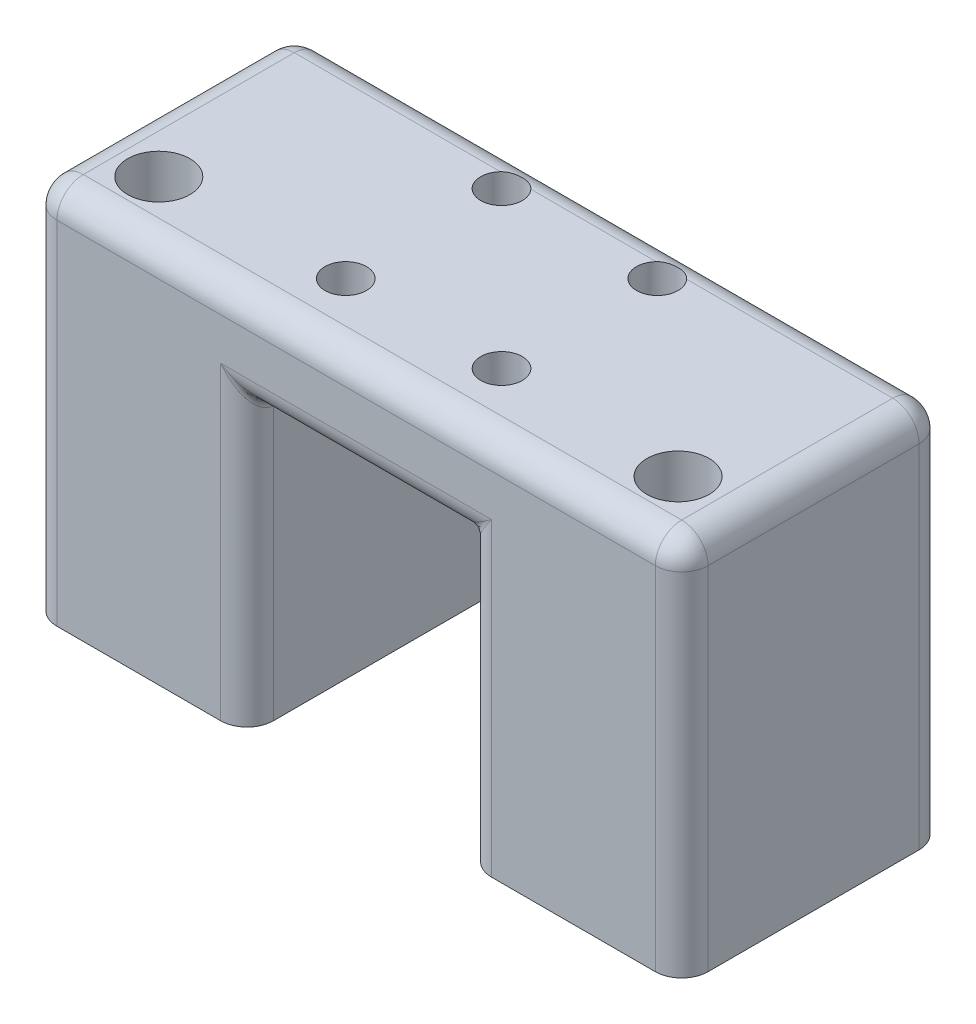
SolidWorks part; units mm, degrees
material "PLA"
ref_plane "Front Plane" through (0, 0, 0) normal (0, 0, 1) x (1, 0, 0)
ref_plane "Top Plane" through (0, 0, 0) normal (0, 1, 0) x (1, 0, 0)
ref_plane "Right Plane" through (0, 0, 0) normal (1, 0, 0) x (0, 0, -1)
sketch "Sketch1" plane through (0, 0, 0) normal (0, 1, 0) x (1, 0, 0)
  line L0 (-7.5, 8.8) -> (7.5, 8.8) construction
  line L1 (-31.35, -12.7) -> (31.35, -12.7)
  line L2 (-31.35, -12.7) -> (-31.35, 12.7)
  line L3 (-31.35, 12.7) -> (31.35, 12.7)
  line L4 (31.35, -12.7) -> (31.35, 12.7)
  line L5 (-31.35, -12.7) -> (31.35, 12.7) construction
  line L6 (-31.35, 12.7) -> (31.35, -12.7) construction
  line L7 (7.5, 8.8) -> (7.5, -6.2) construction
  line L8 (7.5, -6.2) -> (-7.5, -6.2) construction
  line L9 (-7.5, -6.2) -> (-7.5, 8.8) construction
  line L10 (-25, -6.7) -> (25, -6.7) construction
  circle A0 centre (-7.5, -6.2) radius 1.125
  circle A1 centre (-7.5, 8.8) radius 1.125
  circle A2 centre (7.5, 8.8) radius 1.125
  circle A3 centre (7.5, -6.2) radius 1.125
  circle A4 centre (-25, -6.7) radius 1.75
  circle A5 centre (25, -6.7) radius 1.75
  point P0 (0, 0)
  point P15 (0, -6.2)
  point P19 (0, -6.7)
  dimension "D6" = 2.25
  dimension "D8" = 3.5
  dimension "D1" = 62.7
  dimension "D2" = 25.4
  dimension "D3" = 15
  dimension "D4" = 15
  dimension "D5" = 6
  dimension "D7" = 50
  dimension "D9" = 0.5
extrude "Boss-Extrude1" add sketch "Sketch1" along normal mid plane 1.5
sketch "Sketch2" plane through (0, -0.75, 0) normal (0, -1, 0) x (1, 0, 0)
  line L0 (31.35, -12.7) -> (-31.35, -12.7) construction
  line L1 (-31.35, 12.7) -> (-10.5, 12.7)
  line L2 (-31.35, 12.7) -> (-31.35, -12.7)
  line L3 (-31.35, -12.7) -> (-10.5, -12.7)
  line L4 (-10.5, 12.7) -> (-10.5, -12.7)
  line L6 (31.35, 12.7) -> (10.5, 12.7)
  line L7 (31.35, 12.7) -> (31.35, -12.7)
  line L8 (31.35, -12.7) -> (10.5, -12.7)
  line L9 (10.5, 12.7) -> (10.5, -12.7)
  circle A0 centre (-25, 6.7) radius 1.75
  circle A1 centre (25, 6.7) radius 1.75
  circle A2 centre (25, 6.7) radius 1.75 construction
  circle A3 centre (-25, 6.7) radius 1.75 construction
  dimension "D1" = 21
extrude "Boss-Extrude2" add sketch "Sketch2" along normal blind 27.278
sketch "Sketch3" plane through (0, 0.75, 0) normal (0, 1, 0) x (1, 0, 0)
  circle A0 centre (-25, -6.7) radius 3
  circle A1 centre (25, -6.7) radius 3
  dimension "D1" = 6
extrude "Cut-Extrude1" cut sketch "Sketch3" against normal blind 19.05
sketch "Sketch4" plane through (0, 0.75, 0) normal (0, 1, 0) x (1, 0, 0)
  line L1 (-31.35, -12.7) -> (31.35, -12.7)
  line L2 (-31.35, -12.7) -> (-31.35, 12.7)
  line L3 (-31.35, 12.7) -> (31.35, 12.7)
  line L4 (31.35, -12.7) -> (31.35, 12.7)
  line L5 (-31.35, -12.7) -> (31.35, 12.7) construction
  line L6 (-31.35, 12.7) -> (31.35, -12.7) construction
  circle A0 centre (-25, -6.7) radius 3
  circle A1 centre (25, -6.7) radius 3
  circle A2 centre (-7.5, 8.8) radius 2
  circle A3 centre (7.5, 8.8) radius 2
  circle A4 centre (-7.5, -6.2) radius 2
  circle A5 centre (7.5, -6.2) radius 2
  circle A6 centre (-25, -6.7) radius 3 construction
  circle A7 centre (25, -6.7) radius 3 construction
  point P22 (0, 0)
  dimension "D1" = 4
extrude "Boss-Extrude3" add sketch "Sketch4" along normal blind 7.62
fillet "Fillet1" radius 2.54 14 edges at (0, -0.75, -12.7) (31.35, 8.37, 0) (0, 8.37, -12.7) (-31.35, 8.37, 0) (0, 8.37, 12.7) (0, -0.75, 12.7) (31.35, -9.829, 12.7) (31.35, -9.829, -12.7) (10.5, -14.389, -12.7) (-10.5, -14.389, -12.7) (10.5, -14.389, 12.7) (-10.5, -14.389, 12.7) (-31.35, -9.829, -12.7) (-31.35, -9.829, 12.7)
fillet "Fillet2" radius 1 6 edges at (11.244, -0.0061, 11.9561) (11.244, -0.0061, -11.9561) (-11.244, -0.0061, -11.9561) (-11.244, -0.0061, 11.9561) (10.5, -0.75, 0) (-10.5, -0.75, 0)
